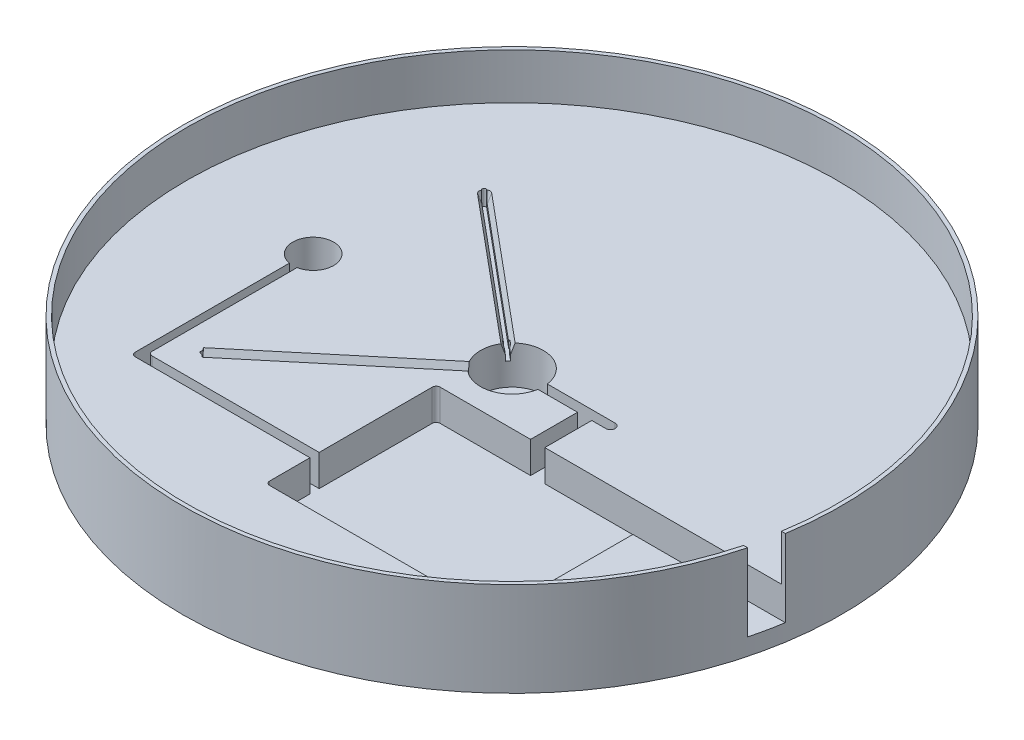
SolidWorks part; units mm, degrees
ref_plane "Front Plane" through (0, 0, 0) normal (0, 0, 1) x (1, 0, 0)
ref_plane "Top Plane" through (0, 0, 0) normal (0, 1, 0) x (1, 0, 0)
ref_plane "Right Plane" through (0, 0, 0) normal (1, 0, 0) x (0, 0, -1)
sketch "Sketch1" plane through (0, 0, 0) normal (0, 1, 0) x (1, 0, 0)
  circle A0 centre (0, 0) radius 266.7
extrude "Boss-Extrude1" add sketch "Sketch1" along normal blind 76.2
sketch "Sketch2" plane through (0, 76.2, 0) normal (0, 1, 0) x (1, 0, 0)
  circle A0 centre (0, 0) radius 263.525
extrude "Cut-Extrude1" cut sketch "Sketch2" against normal blind 37.084
sketch "Sketch3" plane through (0, 39.116, 0) normal (0, 1, 0) x (1, 0, 0)
  circle A0 centre (0, 0) radius 25.4
extrude "Cut-Extrude2" cut sketch "Sketch3" against normal blind 30.988
sketch "Sketch4" plane through (0, 39.116, 0) normal (0, 1, 0) x (1, 0, 0)
  line L0 (3.81, -0.2983) -> (80.01, -0.2983) construction
  line L1 (0, 3.5117) -> (76.2, 3.5117) construction
  line L2 (0, 3.5117) -> (0, -4.1083) construction
  line L3 (0, -4.1083) -> (76.2, -4.1083) construction
  line L4 (76.2, 3.5117) -> (76.2, -4.1083) construction
  line L5 (3.81, 3.5117) -> (80.01, 3.5117)
  line L6 (3.81, -4.1083) -> (80.01, -4.1083)
  line L7 (0, 3.5117) -> (0, -4.1083) construction
  arc A0 (3.81, 3.5117) -> (3.81, -4.1083) centre (3.81, -0.2983) ccw
  arc A1 (80.01, -4.1083) -> (80.01, 3.5117) centre (80.01, -0.2983) ccw
  point P6 (41.91, -0.2983)
extrude "Cut-Extrude3" cut sketch "Sketch4" against normal through all
sketch "Sketch5" plane through (0, 39.116, 0) normal (0, 1, 0) x (1, 0, 0)
  line L0 (0, 0) -> (-39.9134, 33.31) construction
  line L1 (-39.9134, 33.31) -> (-39.9134, -33.31) construction
  line L2 (-39.9134, 0) -> (-42.73, -2.8166) construction
  line L3 (0, 0) -> (-39.9134, 0) construction
  line L4 (-39.9134, 0) -> (-42.73, 2.8166) construction
  line L5 (0, 0) -> (-39.9134, -33.31) construction
  line L6 (0, 0) -> (-136.5075, 113.9234) construction
  line L7 (-0.9765, -1.1701) -> (-137.484, 112.7533)
  line L8 (0.9765, 1.1701) -> (-135.5311, 115.0934)
  line L13 (0, 0) -> (-136.5075, -113.9234) construction
  line L14 (-136.5075, -113.9234) -> (0, 0) construction
  line L15 (-137.484, -112.7533) -> (-0.9765, 1.1701)
  line L16 (-135.5311, -115.0934) -> (0.9765, -1.1701)
  arc A0 (-0.9765, -1.1701) -> (0.9765, 1.1701) centre (0, 0) ccw
  arc A1 (-135.5311, 115.0934) -> (-137.484, 112.7533) centre (-136.5075, 113.9234) ccw
  arc A4 (-137.484, -112.7533) -> (-135.5311, -115.0934) centre (-136.5075, -113.9234) ccw
  arc A5 (0.9765, -1.1701) -> (-0.9765, 1.1701) centre (0, 0) ccw
  point P7 (-68.2538, 56.9617)
  point P24 (-68.2538, -56.9617)
  arc M12 (25.0655, -4.1083) -> (25.1561, 3.5117) centre (0, 0) cw
extrude "Cut-Extrude4" cut sketch "Sketch5" against normal blind 12.7 contours L15 A4 L16 M12 | L7 A1 L8 A0 region at (-78.4582, 39.116, 65.4779)
ref_plane "Plane1" through (-19.4659, 0, -16.2454) normal (0.7678, 0, 0.6407) x (0.6407, 0, -0.7678)
sketch "Sketch6" plane through (-19.4659, 0, -16.2454) normal (0.7678, 0, 0.6407) x (0.6407, 0, -0.7678)
  line L0 (0, 26.416) -> (-4.0671, 39.116)
  line L1 (1.524, 26.416) -> (-1.524, 26.416) construction
  line L2 (-1.524, 39.116) -> (-24.6725, 39.116) construction
  line L3 (-4.0671, 39.116) -> (4.0671, 39.116)
  line L4 (1.524, 39.116) -> (-1.524, 39.116) construction
  line L5 (0, 39.116) -> (0, 26.416) construction
  line L6 (0, 26.416) -> (4.0671, 39.116)
extrude "Cut-Extrude5" cut sketch "Sketch6" against normal blind 152.4 and the other way blind 6.35
ref_plane "Plane2" through (-19.4659, 0, 16.2454) normal (-0.7678, 0, 0.6407) x (0.6407, 0, 0.7678)
sketch "Sketch11" plane through (-19.4659, 0, 16.2454) normal (-0.7678, 0, 0.6407) x (0.6407, 0, 0.7678)
  line L0 (0, 26.416) -> (4.7515, 39.116)
  line L1 (1.524, 26.416) -> (-1.524, 26.416) construction
  line L2 (263.525, 39.116) -> (-263.525, 39.116) construction
  line L3 (4.7515, 39.116) -> (-4.7515, 39.116)
  line L5 (0, 39.4107) -> (0, 26.416) construction
  line L7 (0, 26.416) -> (-4.7515, 39.116)
extrude "Cut-Extrude6" cut sketch "Sketch11" along normal blind 152.4 and the other way blind 6.35
ref_plane "Plane3" through (-24.3412, 0, 20.3141) normal (-0.7678, 0, 0.6407) x (0.6407, 0, 0.7678)
sketch "Sketch12" plane through (-24.3412, 0, 20.3141) normal (-0.7678, 0, 0.6407) x (0.6407, 0, 0.7678)
  line L0 (0, 26.416) -> (0, 31.0485) construction
  line L1 (1.524, 26.416) -> (-1.524, 26.416) construction
  line L2 (2.159, 26.416) -> (-2.159, 26.416) construction
  line L4 (-2.159, 26.416) -> (2.159, 26.416)
  line L7 (-2.159, 26.416) -> (-2.159, 41.4963)
  line L8 (-2.159, 41.4963) -> (2.159, 41.4963)
  line L9 (2.159, 26.416) -> (2.159, 41.4963)
extrude "Cut-Extrude10" cut sketch "Sketch12" along normal blind 6.35
ref_plane "Plane4" through (-24.3412, 0, -20.3141) normal (0.7678, 0, 0.6407) x (0.6407, 0, -0.7678)
sketch "Sketch14" plane through (-24.3412, 0, -20.3141) normal (0.7678, 0, 0.6407) x (0.6407, 0, -0.7678)
  line L0 (-2.159, 39.116) -> (2.159, 39.116) construction
  line L1 (0, 26.416) -> (-2.159, 26.416) construction
  line L2 (1.524, 26.416) -> (-1.524, 26.416) construction
  line L3 (-2.159, 26.416) -> (-2.159, 39.116) construction
  line L4 (2.159, 39.116) -> (2.159, 26.416) construction
  line L5 (2.159, 26.416) -> (0, 26.416) construction
  line L6 (0, 26.416) -> (-0.0449, 26.4266) construction
  line L8 (-2.159, 39.116) -> (2.159, 39.116)
  line L9 (-2.159, 39.116) -> (-2.159, 26.416)
  line L10 (-2.159, 26.416) -> (2.159, 26.416)
  line L11 (2.159, 39.116) -> (2.159, 26.416)
extrude "Cut-Extrude11" cut sketch "Sketch14" against normal blind 6.35
sketch "Sketch15" plane through (0, 39.116, 0) normal (0, 1, 0) x (1, 0, 0)
  line L1 (-163.9443, -16.219) -> (-163.9443, -18.5449)
  line L3 (-157.7721, -16.219) -> (-157.7721, -18.5449)
  line L4 (-163.9443, -18.5449) -> (-157.7721, -18.5449)
  circle A0 centre (0, 0) radius 177.8 construction
  circle A1 centre (-160.8582, 0) radius 16.9418 construction
  arc A2 (-157.7721, -16.219) -> (-163.9443, -16.219) centre (-160.8582, 0) ccw
  point P6 (-160.8582, 0)
extrude "Cut-Extrude12" cut sketch "Sketch15" against normal blind 27.94
fillet "Fillet3" radius 3.175 1 edges at (-22.9579, 29.7868, -21.9717)
fillet "Fillet4" radius 3.175 7 edges at (-27.8331, 29.3014, 26.0404) (-30.5998, 29.3014, 22.7252) (-25.7246, 29.3014, 18.6565) (-22.9579, 29.3014, 21.9717) (-30.5998, 29.7868, -22.7252) (-27.8331, 29.7868, -26.0404) (-25.7246, 29.7868, -18.6565)
fillet "Fillet5" radius 3.175 2 edges at (-134.6812, 35.1454, -116.0404) (-138.2636, 35.1454, -111.7477)
fillet "Fillet6" radius 3.175 2 edges at (-135.4959, 34.8027, 115.0641) (-137.4489, 34.8027, 112.724)
sketch "Sketch18" plane through (0, 39.116, 0) normal (0, 1, 0) x (1, 0, 0)
  line L1 (-19.2383, -180.0452) -> (165.1982, -180.0452)
  line L2 (-19.2383, -180.0452) -> (-19.2383, -144.2581)
  line L3 (-19.2383, -42.1099) -> (57.1594, -42.1099)
  line L4 (165.1982, -180.0452) -> (165.1982, -67.3252)
  line L5 (25.0655, -4.1083) -> (80.01, -4.1083) construction
  line L6 (68.684, -4.1083) -> (57.1594, -4.1083)
  line L7 (68.684, -4.1083) -> (68.684, -42.1099)
  line L8 (-19.2383, -136.806) -> (-19.2383, -42.1099)
  line L9 (57.1594, -4.1083) -> (57.1594, -42.1099)
  line L10 (68.684, -42.1099) -> (165.1982, -42.1099)
  line L11 (-163.9443, -18.5449) -> (-157.6889, -18.5449)
  line L12 (-163.9443, -18.5449) -> (-163.9443, -144.2581)
  line L13 (-163.9443, -144.2581) -> (-157.6889, -144.2581)
  line L14 (-157.6889, -18.5449) -> (-157.6889, -136.806)
  line L15 (-157.6889, -144.2581) -> (-19.2383, -144.2581)
  line L17 (-157.6889, -136.806) -> (-19.2383, -136.806)
  line L18 (165.1982, -42.1099) -> (267.0856, -42.1099)
  line L20 (165.1982, -67.3252) -> (267.0856, -67.3252)
  line L21 (267.0856, -42.1099) -> (267.0856, -67.3252)
extrude "Cut-Extrude13" cut sketch "Sketch18" against normal blind 25.4 and the other way through all
fillet "Fillet8" radius 3.175 5 edges at (165.1982, 26.416, 180.0452) (-19.2383, 26.416, 42.1099) (-19.2383, 26.416, 180.0452) (-163.9443, 26.416, 144.2581) (-157.6889, 26.416, 136.806)
